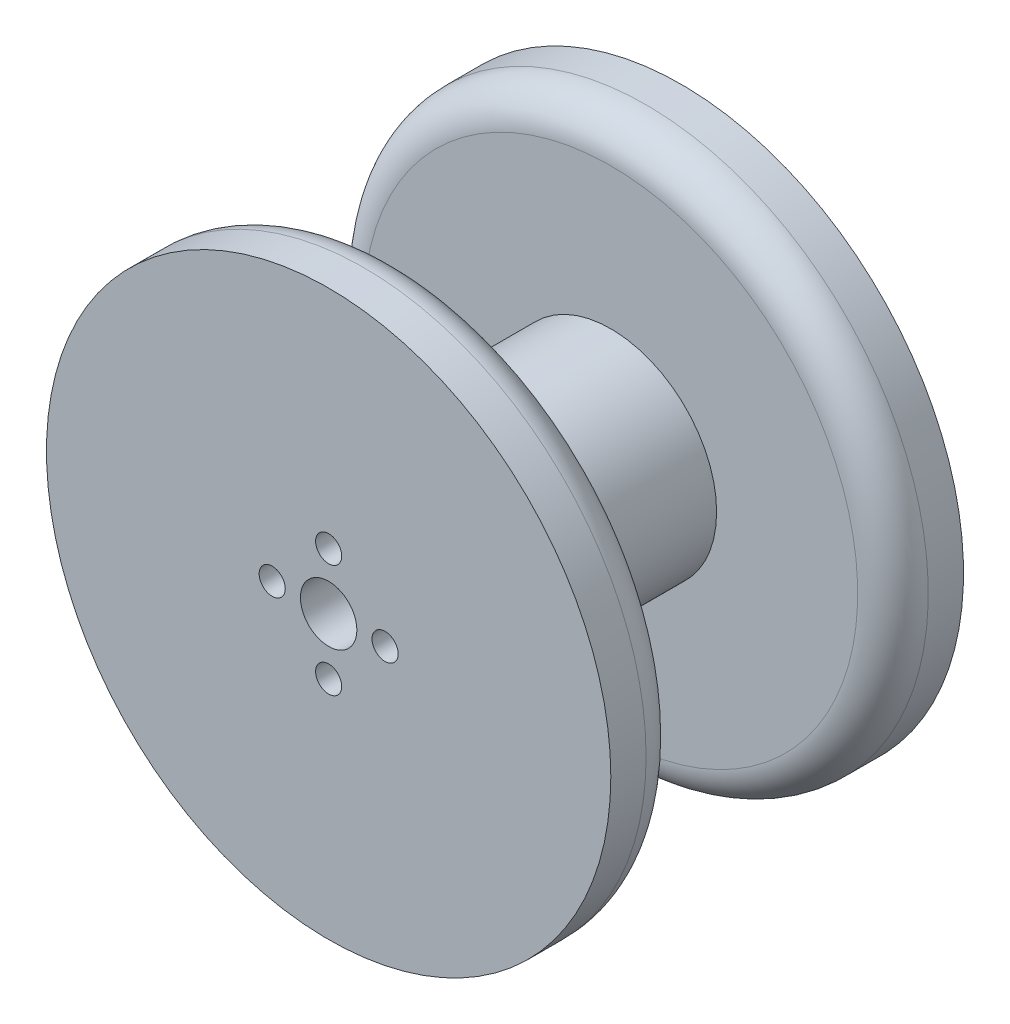
SolidWorks part; units mm, degrees
ref_plane "Front Plane" through (0, 0, 0) normal (0, 0, 1) x (1, 0, 0)
ref_plane "Top Plane" through (0, 0, 0) normal (0, 1, 0) x (1, 0, 0)
ref_plane "Right Plane" through (0, 0, 0) normal (1, 0, 0) x (0, 0, -1)
sketch "Sketch1" plane through (0, 0, 0) normal (0, 0, 1) x (1, 0, 0)
  circle A5 centre (0, 0) radius 40
  dimension "D1" = 80
extrude "Boss-Extrude1" add sketch "Sketch1" along normal blind 10
sketch "Sketch2" plane through (0, 0, 0) normal (0, 0, 1) x (1, 0, 0)
  circle A0 centre (0, 0) radius 15
  dimension "D1" = 30
extrude "Boss-Extrude2" add sketch "Sketch2" against normal blind 30
sketch "Sketch5" plane through (0, 0, -30) normal (0, 0, -1) x (-1, 0, 0)
  circle A2 centre (0, 0) radius 40
  circle A3 centre (0, 0) radius 40
  dimension "D1" = 0
extrude "Boss-Extrude4" add sketch "Sketch5" along normal blind 10
sketch "Sketch6" plane through (0, 0, 10) normal (0, 0, 1) x (1, 0, 0)
  line L0 (0, 0) -> (0, 8) construction
  circle A0 centre (0, 0) radius 4
  circle A1 centre (0, 8) radius 1.85
  circle A2 centre (8, 0) radius 1.85
  circle A3 centre (0, -8) radius 1.85
  circle A4 centre (-8, 0) radius 1.85
  point P14 (0, 0)
  dimension "D1" = 8
  dimension "D3" = 3.7
  dimension "D2" = 8
  dimension "D4" = 4
extrude "Cut-Extrude1" cut sketch "Sketch6" against normal through all
fillet "Fillet1" radius 5 2 edges at (40, 0, 0) (-40, 0, -30)
